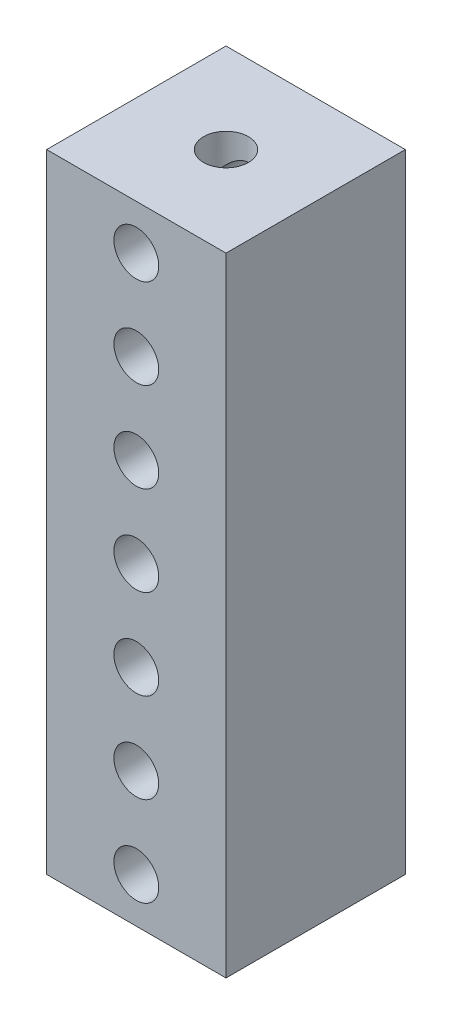
SolidWorks part; units mm, degrees
ref_plane "Front Plane" through (0, 0, 0) normal (0, 0, 1) x (1, 0, 0)
ref_plane "Top Plane" through (0, 0, 0) normal (0, 1, 0) x (1, 0, 0)
ref_plane "Right Plane" through (0, 0, 0) normal (1, 0, 0) x (0, 0, -1)
sketch "Sketch1" plane through (0, 0, 0) normal (0, 1, 0) x (1, 0, 0)
  line L1 (-10, 10) -> (10, 10)
  line L2 (-10, 10) -> (-10, -10)
  line L3 (-10, -10) -> (10, -10)
  line L4 (10, 10) -> (10, -10)
  line L5 (-10, 10) -> (10, -10) construction
  line L6 (-10, -10) -> (10, 10) construction
  circle A0 centre (0, 0) radius 2.5
  point P0 (0, 0)
  dimension "D3" = 5
  dimension "D1" = 20
  dimension "D2" = 20
extrude "Boss-Extrude1" add sketch "Sketch1" along normal blind 70
sketch "Sketch2" plane through (0, 0, 10) normal (0, 0, 1) x (1, 0, 0)
  line L0 (-10, 0) -> (10, 0) construction
  circle A0 centre (0, 5) radius 2.5
  dimension "D1" = 5
  dimension "D2" = 5
extrude "Cut-Extrude1" cut sketch "Sketch2" against normal blind 100
pattern_linear "LPattern1" count 5 spacing 10 along (0, 1, 0) of "Cut-Extrude1"
sketch "Sketch3" plane through (0, 0, 10) normal (0, 0, 1) x (1, 0, 0)
  line L0 (0, -900) -> (0, 49100) construction
  line L1 (-10, 70) -> (10, 70) construction
  circle A0 centre (0, 65) radius 2.5
  circle A1 centre (0, 55) radius 2.5
  point P5 (0, 70)
  dimension "D1" = 5
  dimension "D2" = 5
  dimension "D3" = 5
  dimension "D4" = 15
extrude "Cut-Extrude4" cut sketch "Sketch3" against normal through all
